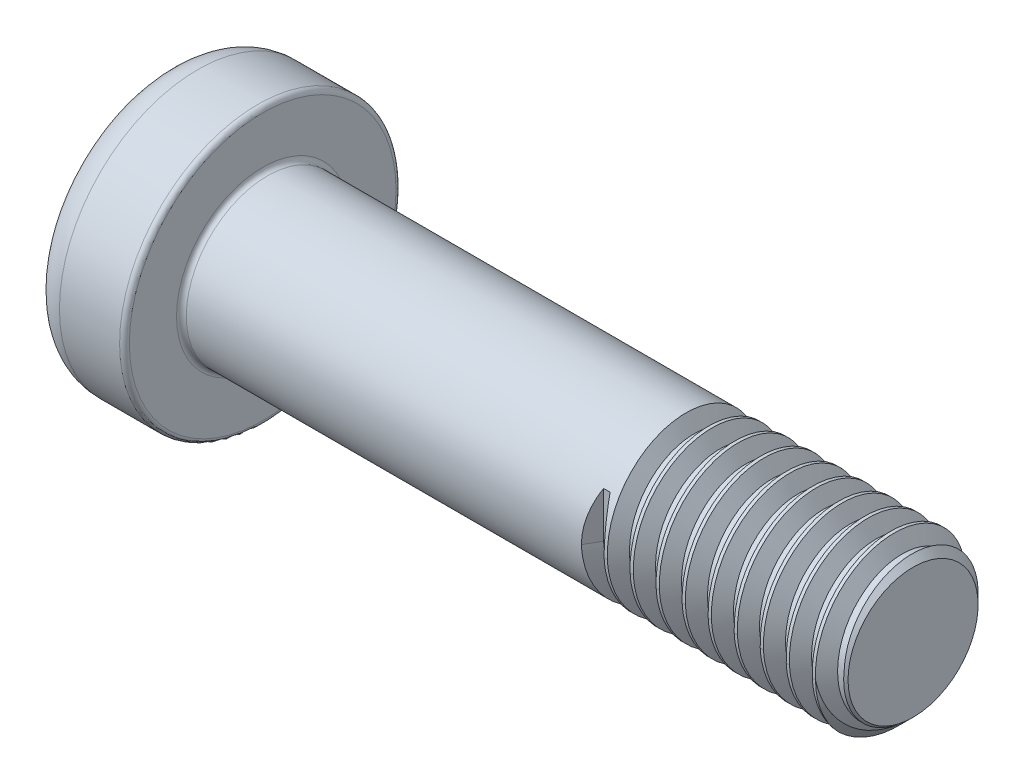
SolidWorks part; units mm, degrees
material "Acier inoxydable chromé"
ref_plane "Front Plane" through (0, 0, 0) normal (0, 0, 1) x (1, 0, 0)
ref_plane "Top Plane" through (0, 0, 0) normal (0, 1, 0) x (1, 0, 0)
ref_plane "Right Plane" through (0, 0, 0) normal (1, 0, 0) x (0, 0, -1)
sketch "Esquisse1" plane through (0, 0, 0) normal (0, 0, 1) x (1, 0, 0)
  line L0 (-10.0862, 0) -> (41.9828, 0) construction
  line L1 (0, 0) -> (0, 3.25)
  line L2 (1, 4.25) -> (3, 4.25)
  line L3 (3, 4.25) -> (3, 2.5)
  line L4 (3, 2.5) -> (23, 2.5)
  line L5 (23, 2.5) -> (23, 0)
  line L6 (23, 0) -> (0, 0)
  arc A0 (1, 4.25) -> (0, 3.25) centre (1, 3.25) ccw
  point P11 (0, 4.25)
  dimension "D5" = 1
  dimension "D1" = 5
  dimension "D4" = 8.5
revolve "Révolution1" add sketch "Esquisse1" angle 360 about L0
chamfer "Chanfrein1" distance 0.5 angle 45 1 edges at (23, 0, 2.5)
sketch "Esquisse2" plane through (0, 0, 0) normal (-1, 0, 0) x (0, 0, 1)
  line L1 (-2, 1.1547) -> (-2, -1.1547)
  line L2 (-2, -1.1547) -> (0, -2.3094)
  line L3 (0, -2.3094) -> (2, -1.1547)
  line L4 (2, -1.1547) -> (2, 1.1547)
  line L5 (2, 1.1547) -> (0, 2.3094)
  line L6 (0, 2.3094) -> (-2, 1.1547)
  circle A0 centre (0, 0) radius 2 construction
  dimension "D1" = 4
extrude "Enlèv. mat.-Extru.1" cut sketch "Esquisse2" against normal blind 3.5
sketch "Esquisse3" plane through (0, 0, 0) normal (0, 0, 1) x (1, 0, 0)
  line L0 (3.5, 0) -> (3.5, 2.3)
  line L1 (3.5, 1.1547) -> (3.5, -1.1547) construction
  line L2 (3.5, 2.3094) -> (3.5, 1.1547) construction
  line L3 (3.5, 2.3) -> (4, 0)
  line L4 (4, 0) -> (3.5, 0)
  line L5 (-3.9508, 0) -> (9.9229, 0) construction
  dimension "D1" = 2.3
  dimension "D2" = 0.5
revolve "Enlèvement de matière-Révolution1" cut sketch "Esquisse3" angle 360 about L5
fillet "Congé2" radius 0.15 8 edges at (0, -1.7321, -1) (0, -1.7321, 1) (0, 0, 2) (0, 1.7321, 1) (0, 1.7321, -1) (0, 0, -2) (3, 0, 2.5) (3, 0, 4.25)
thread "Filetage1" pitch 0.8 method cut profile "Profil de filetage1" start angle 0, offset 1, length 8, pitch 0.8, diameter 5
ref_plane "Plan1" through (24, 0, 2.5) normal (0, -1, 0) x (0, 0, 1)
sketch "Profil de filetage1" plane through (24, 0, 2.5) normal (0, -1, 0) x (0, 0, 1)
  line L0 (0, 0) -> (0, 0.8) construction
  line L11 (0, 0) -> (0, 0.7)
  line L12 (0, 0.7) -> (-0.433, 0.45)
  line L13 (-0.433, 0.45) -> (-0.433, 0.25)
  line L15 (-0.433, 0.25) -> (0, 0)
  line L17 (-0.433, 0.35) -> (0, 0.35) construction
  point P2 (0, 0)
  dimension "Pitch" = 0.8
  dimension "Profile_Angle" = 60
  dimension "Profile_Land" = 0.2
  dimension "Profile_Height" = 0.433
sketch "Esquisse6" plane through (0, 0, 0) normal (0, -1, 0) x (1, 0, 0)
  line L4 (15.75, 2.067) -> (16, 2.5)
  line L5 (16, 2.5) -> (15.3, 2.5)
  line L6 (15.3, 2.5) -> (15.55, 2.067)
  line L7 (15.55, 2.067) -> (15.75, 2.067)
  line L8 (15.75, 2.067) -> (16, 2.5)
  line L10 (15.3, 2.5) -> (15.55, 2.067)
  line L11 (15.55, 2.067) -> (15.75, 2.067)
  line L18 (16, 2.5) -> (15.3, 2.5)
  dimension "D1" = 0
extrude "Enlèv. mat.-Extru.2" cut sketch "Esquisse6" against normal blind 3.5
equation "\"Diametre\"= 5mm"
equation "\"Longueur\"= 35mm"
equation "\"D1@Esquisse1\"=\"Diametre\""
equation "\"HauteurTete\"= 5mm"
equation "\"Empreinte\"= 4mm"
equation "\"Chanfrein\"= 0.5mm"
equation "\"CongéSec\"= 0.15mm"
equation "\"DiametreTete\"= 8.5mm"
equation "\"D4@Esquisse1\"=\"DiametreTete\""
equation "\"D1@Chanfrein1\"=\"Chanfrein\""
equation "\"D1@Esquisse2\"=\"Empreinte\""
equation "\"D1@Congé2\"=\"CongéSec\""
equation "\"LongueurFil\"= 26mm"
equation "\"D4@Filetage1\" = \"LongueurFil\""
